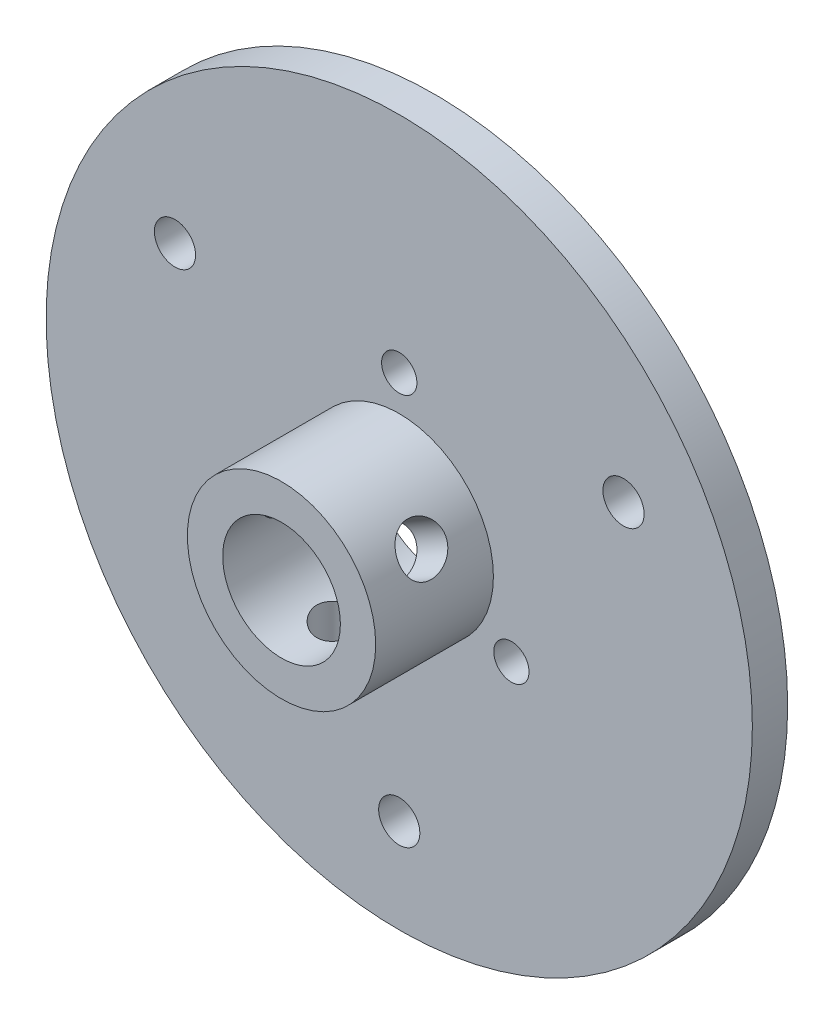
SolidWorks part; units mm, degrees
ref_plane "Front Plane" through (0, 0, 0) normal (0, 0, 1) x (1, 0, 0)
ref_plane "Top Plane" through (0, 0, 0) normal (0, 1, 0) x (1, 0, 0)
ref_plane "Right Plane" through (0, 0, 0) normal (1, 0, 0) x (0, 0, -1)
sketch "Sketch2" plane through (0, 0, 0) normal (0, 0, 1) x (1, 0, 0)
  circle A0 centre (0, 0) radius 5
  circle A2 centre (0, 0) radius 22 construction
  circle A3 centre (0, 0) radius 30
  circle A4 centre (0, -22) radius 1.75
  circle A5 centre (-19.0526, 11) radius 1.75
  circle A6 centre (19.0526, 11) radius 1.75
  point P13 (0, 0)
  dimension "D1" = 3
  dimension "D2" = 44
  dimension "D3" = 3.5
  dimension "D4" = 10
  dimension "D5" = 60
extrude "Boss-Extrude1" add sketch "Sketch2" along normal blind 3
sketch "Sketch3" plane through (0, 0, 3) normal (0, 0, 1) x (1, 0, 0)
  circle A0 centre (0, 0) radius 8
  circle A1 centre (0, 0) radius 5
  dimension "D1" = 16
extrude "Boss-Extrude2" add sketch "Sketch3" along normal blind 10
sketch "Sketch4" plane through (0, 0, 3) normal (0, 0, 1) x (1, 0, 0)
  circle A10 centre (0, 11) radius 1.5
  circle A11 centre (9.5263, -5.5) radius 1.5
  circle A12 centre (-9.5263, -5.5) radius 1.5
  point P11 (0, 0)
  point P12 (0, 0)
  point P13 (0, 0)
  dimension "D1" = 3
  dimension "D2" = 3
  dimension "D3" = 11
extrude "Cut-Extrude2" cut sketch "Sketch4" against normal through all contours A12 | A11 | A10
sketch "Sketch12" plane through (0, 0, 0) normal (0, 1, 0) x (1, 0, 0)
  circle A0 centre (0, -8) radius 2
  dimension "D1" = 4
  dimension "D2" = 8
extrude "Cut-Extrude3" cut sketch "Sketch12" against normal blind 11.4938
pattern_circular "CirPattern1" count 3 every 120 about axis through (0, 0, 13) along (0, 0, 1) of "Cut-Extrude3"
